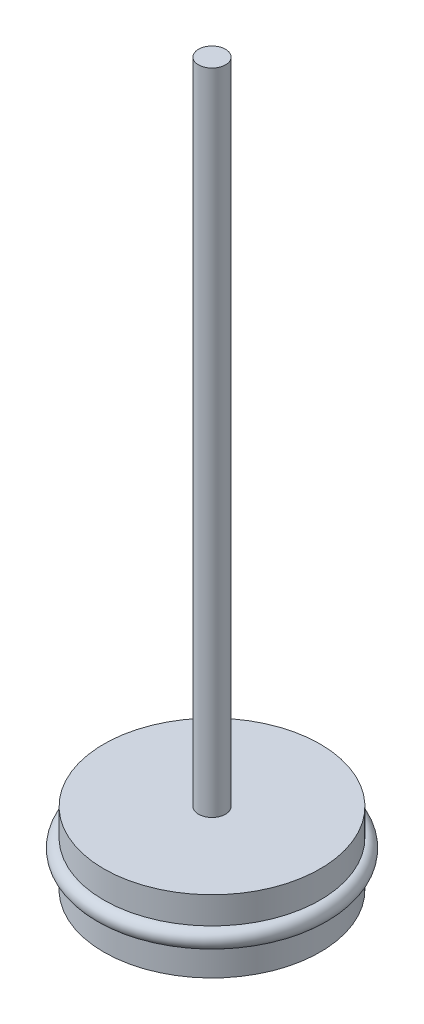
SolidWorks part; units mm, degrees
ref_plane "Front Plane" through (0, 0, 0) normal (0, 0, 1) x (1, 0, 0)
ref_plane "Top Plane" through (0, 0, 0) normal (0, 1, 0) x (1, 0, 0)
ref_plane "Right Plane" through (0, 0, 0) normal (1, 0, 0) x (0, 0, -1)
sketch "Sketch1" plane through (0, 0, 0) normal (0, 1, 0) x (1, 0, 0)
  circle A0 centre (0, 0) radius 12
  circle A1 centre (0, 0) radius 1.5
extrude "Boss-Extrude1" add sketch "Sketch1" along normal blind 3
sketch "Sketch3" plane through (0, 0, 0) normal (0, 0, 1) x (1, 0, 0)
  line L1 (0, 3) -> (0, 6.0318)
  line L2 (12, 3) -> (-12, 3) construction
  circle A0 centre (-12, 4) radius 1
  dimension "D1" = 2
revolve "Revolve1" add sketch "Sketch3" angle 360 about L1 region at (-12, 4, 0)
extrude "Boss-Extrude2" add sketch "Sketch1<2>" along normal blind 3 from offset 5 separate body
sketch "Sketch1<2>" plane through (0, 0, 0) normal (0, 1, 0) x (1, 0, 0) same geometry as "Sketch1"
extrude "Boss-Extrude3" add sketch "Sketch1<3>" along normal blind 80 contours A1 region at (0, 0, 0)
sketch "Sketch1<3>" plane through (0, 0, 0) normal (0, 1, 0) x (1, 0, 0) same geometry as "Sketch1"
cosmetic thread "Cosmetic Thread1" parameters "D1"=11, "D2"=2
